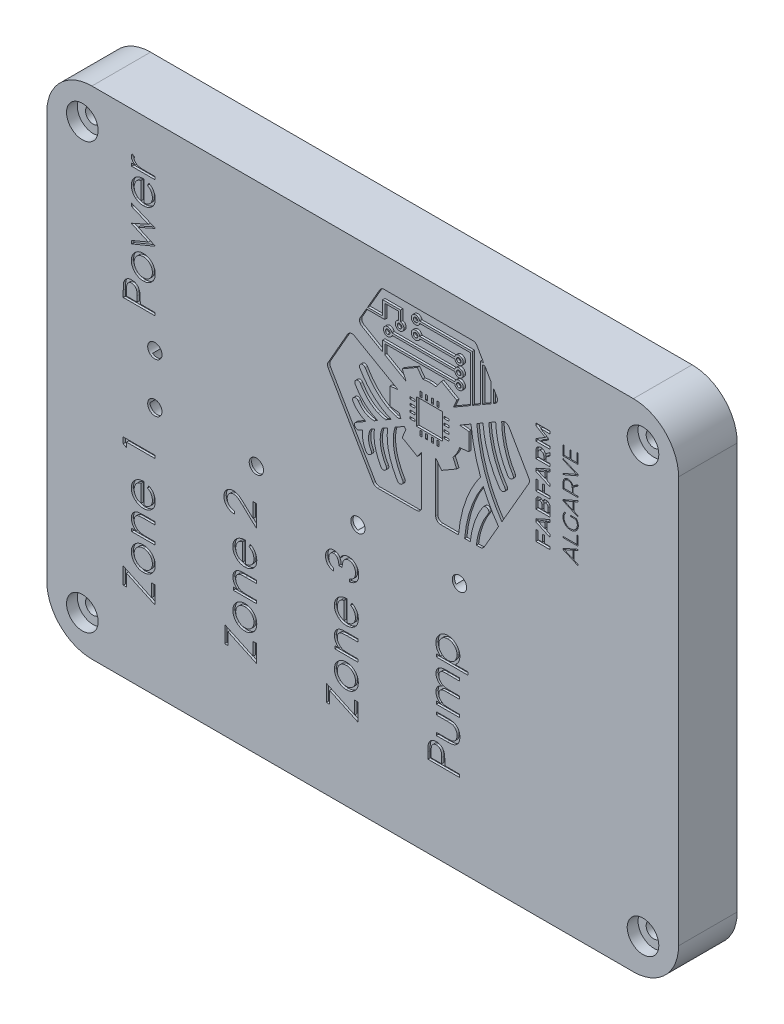
SolidWorks part; units mm, degrees
ref_plane "Front Plane" through (0, 0, 0) normal (0, 0, 1) x (1, 0, 0)
ref_plane "Top Plane" through (0, 0, 0) normal (0, 1, 0) x (1, 0, 0)
ref_plane "Right Plane" through (0, 0, 0) normal (1, 0, 0) x (0, 0, -1)
sketch "Sketch1" plane through (0, 0, 0) normal (0, 0, 1) x (1, 0, 0)
  line L0 (128.6764, 77.0848) -> (128.6764, -12.9152) construction
  line L1 (118.6764, -22.9152) -> (-1.3236, -22.9152) construction
  line L2 (-11.3236, -12.9152) -> (-11.3236, 77.0848) construction
  line L3 (-1.3236, 87.0848) -> (118.6764, 87.0848) construction
  line L4 (128.6764, 77.0848) -> (128.6764, -12.9152)
  line L5 (118.6764, -22.9152) -> (-1.3236, -22.9152)
  line L6 (-11.3236, -12.9152) -> (-11.3236, 77.0848)
  line L7 (-1.3236, 87.0848) -> (118.6764, 87.0848)
  arc A0 (128.6764, 77.0848) -> (118.6764, 87.0848) centre (118.6764, 77.0848) ccw construction
  arc A1 (118.6764, -22.9152) -> (128.6764, -12.9152) centre (118.6764, -12.9152) ccw construction
  arc A2 (-11.3236, -12.9152) -> (-1.3236, -22.9152) centre (-1.3236, -12.9152) ccw construction
  arc A3 (-1.3236, 87.0848) -> (-11.3236, 77.0848) centre (-1.3236, 77.0848) ccw construction
  arc A4 (128.6764, 77.0848) -> (118.6764, 87.0848) centre (118.6764, 77.0848) ccw
  arc A5 (118.6764, -22.9152) -> (128.6764, -12.9152) centre (118.6764, -12.9152) ccw
  arc A6 (-11.3236, -12.9152) -> (-1.3236, -22.9152) centre (-1.3236, -12.9152) ccw
  arc A7 (-1.3236, 87.0848) -> (-11.3236, 77.0848) centre (-1.3236, 77.0848) ccw
extrude "Boss-Extrude1" add sketch "Sketch1" along normal offset from surface (13 mm away) 6 offset beyond the face yes
sketch "Sketch12" plane through (0, 0, 0) normal (0, 0, -1) x (-1, 0, 0)
  line L8 (1.3236, -6.9152) -> (1.3236, 70.5848)
  line L9 (-5.1764, 77.0848) -> (-109.6764, 77.0848)
  line L10 (-118.6764, 68.0848) -> (-118.6764, -3.9152)
  line L11 (-109.6764, -12.9152) -> (-7.6764, -12.9152)
  line L16 (-5.1764, 74.0848) -> (-5.1764, 77.0848)
  line L18 (-1.6764, -6.9152) -> (1.3236, -6.9152)
  line L20 (1.3236, 70.5848) -> (-1.6764, 70.5848)
  arc A25 (-5.1764, 74.0848) -> (-1.6764, 70.5848) centre (-1.6764, 74.0848) ccw
  arc A27 (-109.6764, 77.0848) -> (-112.6764, 74.0848) centre (-109.6764, 74.0848) ccw
  arc A28 (-115.6764, 71.0848) -> (-112.6764, 74.0848) centre (-115.6764, 74.0848) ccw
  arc A29 (-115.6764, 71.0848) -> (-118.6764, 68.0848) centre (-115.6764, 68.0848) ccw
  arc A30 (-118.6764, -3.9152) -> (-115.6764, -6.9152) centre (-115.6764, -3.9152) ccw
  arc A31 (-112.6764, -9.9152) -> (-115.6764, -6.9152) centre (-115.6764, -9.9152) ccw
  arc A32 (-112.6764, -9.9152) -> (-109.6764, -12.9152) centre (-109.6764, -9.9152) ccw
  arc A33 (-7.6764, -12.9152) -> (-4.6764, -9.9152) centre (-7.6764, -9.9152) ccw
  arc A34 (-1.6764, -6.9152) -> (-4.6764, -9.9152) centre (-1.6764, -9.9152) ccw
extrude "Cut-Extrude6" [suppressed] cut sketch "Sketch12" against normal offset from surface (10 mm away) 3 up to face at (58.6764, 32.0848, 13)
sketch "Sketch2" plane through (0, 0, 0) normal (0, 0, -1) x (-1, 0, 0)
  line L2 (1.3236, -6.9152) -> (1.3236, 70.5848)
  line L34 (-5.1764, 77.0848) -> (-109.6764, 77.0848)
  line L35 (-118.6764, 68.0848) -> (-118.6764, -3.9152)
  line L36 (-109.6764, -12.9152) -> (-7.6764, -12.9152)
  line L37 (-5.1764, 74.0848) -> (-5.1764, 77.0848)
  line L38 (-1.6764, -6.9152) -> (1.3236, -6.9152)
  line L39 (1.3236, 70.5848) -> (-1.6764, 70.5848)
  arc A0 (-5.1764, 74.0848) -> (-1.6764, 70.5848) centre (-1.6764, 74.0848) ccw
  arc A1 (-109.6764, 77.0848) -> (-112.6764, 74.0848) centre (-109.6764, 74.0848) ccw
  arc A2 (-115.6764, 71.0848) -> (-112.6764, 74.0848) centre (-115.6764, 74.0848) ccw
  arc A3 (-115.6764, 71.0848) -> (-118.6764, 68.0848) centre (-115.6764, 68.0848) ccw
  arc A4 (-118.6764, -3.9152) -> (-115.6764, -6.9152) centre (-115.6764, -3.9152) ccw
  arc A5 (-112.6764, -9.9152) -> (-115.6764, -6.9152) centre (-115.6764, -9.9152) ccw
  arc A14 (-112.6764, -9.9152) -> (-109.6764, -12.9152) centre (-109.6764, -9.9152) ccw
  arc A23 (-7.6764, -12.9152) -> (-4.6764, -9.9152) centre (-7.6764, -9.9152) ccw
  arc A24 (-1.6764, -6.9152) -> (-4.6764, -9.9152) centre (-1.6764, -9.9152) ccw
  point P57 (-115.6764, -9.9152)
extrude "Cut-Extrude1" cut sketch "Sketch2" against normal offset from surface (10 mm away) 3 up to face at (58.6764, 32.0848, 13)
hole_wizard "CBORE for M3 Pan Head Screw1" positions "Sketch3" profile "Sketch4" counterbore size "M3" standard "ISO"
sketch "Sketch3" plane through (0, 0, 13) normal (0, 0, 1) x (1, 0, 0)
  point P0 (-3.4449, -15.0365)
  point P3 (120.7977, -15.0365)
  point P6 (120.7977, 79.2061)
  point P9 (-3.4449, 79.2061)
sketch "Sketch4" plane through (-3.4449, -15.0365, 13) normal (1, 0, 0) x (0, -1, 0)
  line L0 (0, 0) -> (0, 16.0215)
  line L1 (0, 16.0215) -> (1.7, 15)
  line L2 (1.7, 15) -> (1.7, 2.4)
  line L3 (1.7, 2.4) -> (3.5, 2.4)
  line L4 (3.5, 2.4) -> (3.5, 0)
  line L5 (3.5, 0) -> (0, 0)
  line L10 (0, 16.0215) -> (-1.7, 15) construction
  line L11 (0, -6.35) -> (0, 107.95) construction
  dimension "Hole Dia." = 3.4
  dimension "Hole Depth" = 15
  dimension "C'Bore Dia." = 7
  dimension "C'Bore Depth" = 2.4
  dimension "Drill Angle" = 118
fillet "Fillet1" radius 3 3 edges at (-1.3236, -6.9152, 5) (-1.3236, 70.5848, 5) (5.1764, 77.0848, 5)
sketch "Sketch5" plane through (0, 0, 13) normal (0, 0, 1) x (1, 0, 0)
  line L0 (12.6214, 32.3367) -> (99.9994, 32.3367) construction
  line L1 (99.9994, 0) -> (99.9994, 70) construction
  line L2 (12.6214, 32.3367) -> (12.6214, 48.4676) construction
  line L9 (12.6214, 33.064) -> (12.6214, 29) construction
  line L10 (11.6054, 33.064) -> (13.6374, 33.064) construction
  line L11 (13.6374, 29) -> (11.6054, 29) construction
  line L12 (60.1722, 44.4436) -> (58.5466, 44.4436) construction
  line L13 (60.1722, 45.4025) -> (60.1722, 43.4848) construction
  line L14 (58.5466, 45.4025) -> (58.5466, 43.4848) construction
  line L15 (59.3594, 44.4436) -> (59.3594, 47.8324) construction
  circle A0 centre (12.6214, 32.3367) radius 1.5875
  circle A1 centre (35.1214, 32.3367) radius 1.5875
  circle A2 centre (57.6214, 32.3367) radius 1.5875
  circle A3 centre (80.1214, 32.3367) radius 1.5875
  circle A4 centre (12.6214, 43.2728) radius 1.5875
  dimension "D1" = 3.175
  dimension "D2" = 3.175
  dimension "D3" = 3.175
  dimension "D4" = 3.175
  dimension "D8" = 3.175
  dimension "D5" = 22.5
  dimension "D6" = 22.5
  dimension "D7" = 22.5
extrude "Cut-Extrude2" cut sketch "Sketch5" against normal blind 2.5
sketch "Sketch6" plane through (0, 0, 10) normal (0, 0, -1) x (-1, 0, 0)
  circle A0 centre (-12.6214, 31.032) radius 2
  circle A1 centre (-35.2293, 31.7818) radius 2
  circle A2 centre (-55.3902, 31.7818) radius 2
  circle A3 centre (-79.0825, 33.3273) radius 2
  circle A4 centre (-12.0944, 40.0848) radius 2
  dimension "D1" = 4
  dimension "D2" = 4
  dimension "D3" = 4
extrude "Cut-Extrude3" cut sketch "Sketch6" against normal blind 2.5
sketch "Sketch8" plane through (0, 0, 10) normal (0, 0, -1) x (-1, 0, 0)
  line L6 (1.3236, -3.9152) -> (1.3236, 67.5848)
  line L7 (1.3236, -3.9152) -> (1.3236, 67.5848)
  line L19 (-8.1764, 77.0848) -> (-109.6764, 77.0848)
  line L20 (-8.1764, 77.0848) -> (-109.6764, 77.0848)
  line L21 (-118.6764, 68.0848) -> (-118.6764, -3.9152)
  line L22 (-118.6764, 68.0848) -> (-118.6764, -3.9152)
  line L23 (-109.6764, -12.9152) -> (-7.6764, -12.9152)
  line L24 (-109.6764, -12.9152) -> (-7.6764, -12.9152)
  circle A0 centre (-12.0944, 40.0848) radius 4
  circle A1 centre (-12.0944, 40.0848) radius 2 construction
  circle A2 centre (-12.0944, 40.0848) radius 2
  arc A9 (-5.1764, 74.0848) -> (-1.6764, 70.5848) centre (-1.6764, 74.0848) ccw
  arc A10 (-5.1764, 74.0848) -> (-1.6764, 70.5848) centre (-1.6764, 74.0848) ccw
  arc A11 (-109.6764, 77.0848) -> (-112.6764, 74.0848) centre (-109.6764, 74.0848) ccw
  arc A12 (-109.6764, 77.0848) -> (-112.6764, 74.0848) centre (-109.6764, 74.0848) ccw
  arc A13 (-115.6764, 71.0848) -> (-112.6764, 74.0848) centre (-115.6764, 74.0848) ccw
  arc A14 (-115.6764, 71.0848) -> (-112.6764, 74.0848) centre (-115.6764, 74.0848) ccw
  arc A15 (-115.6764, 71.0848) -> (-118.6764, 68.0848) centre (-115.6764, 68.0848) ccw
  arc A16 (-115.6764, 71.0848) -> (-118.6764, 68.0848) centre (-115.6764, 68.0848) ccw
  arc A17 (-118.6764, -3.9152) -> (-115.6764, -6.9152) centre (-115.6764, -3.9152) ccw
  arc A18 (-118.6764, -3.9152) -> (-115.6764, -6.9152) centre (-115.6764, -3.9152) ccw
  arc A19 (-112.6764, -9.9152) -> (-115.6764, -6.9152) centre (-115.6764, -9.9152) ccw
  arc A20 (-112.6764, -9.9152) -> (-115.6764, -6.9152) centre (-115.6764, -9.9152) ccw
  arc A21 (-112.6764, -9.9152) -> (-109.6764, -12.9152) centre (-109.6764, -9.9152) ccw
  arc A22 (-112.6764, -9.9152) -> (-109.6764, -12.9152) centre (-109.6764, -9.9152) ccw
  arc A23 (-7.6764, -12.9152) -> (-4.6764, -9.9152) centre (-7.6764, -9.9152) ccw
  arc A36 (-7.6764, -12.9152) -> (-4.6764, -9.9152) centre (-7.6764, -9.9152) ccw
  arc A37 (-1.6764, -6.9152) -> (-4.6764, -9.9152) centre (-1.6764, -9.9152) ccw
  arc A38 (-1.6764, -6.9152) -> (-4.6764, -9.9152) centre (-1.6764, -9.9152) ccw
  arc A42 (-1.6764, -6.9152) -> (1.3236, -3.9152) centre (-1.6764, -3.9152) ccw
  arc A43 (-1.6764, -6.9152) -> (1.3236, -3.9152) centre (-1.6764, -3.9152) ccw
  arc A44 (1.3236, 67.5848) -> (-1.6764, 70.5848) centre (-1.6764, 67.5848) ccw
  arc A45 (1.3236, 67.5848) -> (-1.6764, 70.5848) centre (-1.6764, 67.5848) ccw
  arc A46 (-5.1764, 74.0848) -> (-8.1764, 77.0848) centre (-8.1764, 74.0848) ccw
  arc A47 (-5.1764, 74.0848) -> (-8.1764, 77.0848) centre (-8.1764, 74.0848) ccw
  circle A95 centre (-12.6214, 31.032) radius 2 construction
  circle A98 centre (-12.6214, 31.032) radius 2
  circle A101 centre (-35.2293, 31.7818) radius 2 construction
  circle A106 centre (-35.2293, 31.7818) radius 2
  circle A115 centre (-55.3902, 31.7818) radius 2 construction
  circle A116 centre (-55.3902, 31.7818) radius 2
  circle A117 centre (-79.0825, 33.3273) radius 2 construction
  circle A118 centre (-79.0825, 33.3273) radius 2
  circle A119 centre (-12.6214, 31.032) radius 4
  circle A120 centre (-35.2293, 31.7818) radius 4
  circle A121 centre (-55.3902, 31.7818) radius 4
  circle A122 centre (-79.0825, 33.3273) radius 4
  circle M21 centre (-12.6214, 31.032) radius 2
  circle M22 centre (-55.3902, 31.7818) radius 2
  circle M23 centre (-35.2293, 31.7818) radius 2
  circle M24 centre (-79.0825, 33.3273) radius 2
  dimension "D3" = 2
  dimension "D1" = 0
  dimension "D2" = 2
extrude "Boss-Extrude2" add sketch "Sketch8" along normal offset from surface (6.3048 mm away) 1 contours A122 M24 | A121 M22 | A120 M23 | A119 M21 region at (16.5083, 31.032, 10) region at (39.1162, 31.7818, 10) region at (59.277, 31.7818, 10) region at (82.9694, 33.3273, 10)
sketch "Sketch10" plane through (0, 0, 0) normal (0, 0, -1) x (-1, 0, 0)
  line L0 (-121.1764, 74.0848) -> (-120.1764, 74.0848)
  line L1 (-115.6764, 78.5848) -> (-115.6764, 79.5848)
  line L2 (-111.1764, 84.0848) -> (-6.1764, 84.0848)
  line L3 (-1.6764, 79.5848) -> (-1.6764, 78.5848)
  line L21 (2.8236, 74.0848) -> (3.8236, 74.0848)
  line L22 (8.3236, 69.5848) -> (8.3236, -5.4152)
  line L23 (3.8236, -9.9152) -> (2.8236, -9.9152)
  line L24 (-1.6764, -14.4152) -> (-1.6764, -15.4152)
  line L25 (-6.1764, -19.9152) -> (-111.1764, -19.9152)
  line L26 (-115.6764, -15.4152) -> (-115.6764, -14.4152)
  line L27 (-120.1764, -9.9152) -> (-121.1764, -9.9152)
  line L28 (-125.6764, -5.4152) -> (-125.6764, 69.5848)
  line L918 (-121.1764, 73.0848) -> (-120.1764, 73.0848)
  line L919 (-121.1764, 73.0848) -> (-120.1764, 73.0848)
  line L926 (-114.6764, 78.5848) -> (-114.6764, 79.5848)
  line L927 (-111.1764, 83.0848) -> (-6.1764, 83.0848)
  line L928 (-2.6764, 79.5848) -> (-2.6764, 78.5848)
  line L929 (2.8236, 73.0848) -> (3.8236, 73.0848)
  line L930 (7.3236, 69.5848) -> (7.3236, -5.4152)
  line L931 (3.8236, -8.9152) -> (2.8236, -8.9152)
  line L932 (-2.6764, -14.4152) -> (-2.6764, -15.4152)
  line L933 (-6.1764, -18.9152) -> (-111.1764, -18.9152)
  line L934 (-114.6764, -15.4152) -> (-114.6764, -14.4152)
  line L935 (-120.1764, -8.9152) -> (-121.1764, -8.9152)
  line L936 (-124.6764, -5.4152) -> (-124.6764, 69.5848)
  line L937 (-114.6764, 78.5848) -> (-114.6764, 79.5848)
  line L938 (-111.1764, 83.0848) -> (-6.1764, 83.0848)
  line L939 (-2.6764, 79.5848) -> (-2.6764, 78.5848)
  line L940 (2.8236, 73.0848) -> (3.8236, 73.0848)
  line L941 (7.3236, 69.5848) -> (7.3236, -5.4152)
  line L942 (3.8236, -8.9152) -> (2.8236, -8.9152)
  line L943 (-2.6764, -14.4152) -> (-2.6764, -15.4152)
  line L944 (-6.1764, -18.9152) -> (-111.1764, -18.9152)
  line L945 (-114.6764, -15.4152) -> (-114.6764, -14.4152)
  line L946 (-120.1764, -8.9152) -> (-121.1764, -8.9152)
  line L947 (-124.6764, -5.4152) -> (-124.6764, 69.5848)
  arc A0 (-120.1764, 74.0848) -> (-115.6764, 78.5848) centre (-120.1764, 78.5848) ccw
  arc A1 (-111.1764, 84.0848) -> (-115.6764, 79.5848) centre (-111.1764, 79.5848) ccw
  arc A2 (-1.6764, 79.5848) -> (-6.1764, 84.0848) centre (-6.1764, 79.5848) ccw
  arc A3 (-1.6764, 78.5848) -> (2.8236, 74.0848) centre (2.8236, 78.5848) ccw
  arc A16 (8.3236, 69.5848) -> (3.8236, 74.0848) centre (3.8236, 69.5848) ccw
  arc A17 (3.8236, -9.9152) -> (8.3236, -5.4152) centre (3.8236, -5.4152) ccw
  arc A18 (2.8236, -9.9152) -> (-1.6764, -14.4152) centre (2.8236, -14.4152) ccw
  arc A19 (-6.1764, -19.9152) -> (-1.6764, -15.4152) centre (-6.1764, -15.4152) ccw
  arc A20 (-115.6764, -15.4152) -> (-111.1764, -19.9152) centre (-111.1764, -15.4152) ccw
  arc A21 (-115.6764, -14.4152) -> (-120.1764, -9.9152) centre (-120.1764, -14.4152) ccw
  arc A22 (-125.6764, -5.4152) -> (-121.1764, -9.9152) centre (-121.1764, -5.4152) ccw
  arc A23 (-121.1764, 74.0848) -> (-125.6764, 69.5848) centre (-121.1764, 69.5848) ccw
  arc A1014 (-121.1764, 73.0848) -> (-124.6764, 69.5848) centre (-121.1764, 69.5848) ccw
  arc A1015 (-121.1764, 73.0848) -> (-124.6764, 69.5848) centre (-121.1764, 69.5848) ccw
  arc A1023 (-120.1764, 73.0848) -> (-114.6764, 78.5848) centre (-120.1764, 78.5848) ccw
  arc A1024 (-111.1764, 83.0848) -> (-114.6764, 79.5848) centre (-111.1764, 79.5848) ccw
  arc A1025 (-2.6764, 79.5848) -> (-6.1764, 83.0848) centre (-6.1764, 79.5848) ccw
  arc A1026 (-2.6764, 78.5848) -> (2.8236, 73.0848) centre (2.8236, 78.5848) ccw
  arc A1027 (7.3236, 69.5848) -> (3.8236, 73.0848) centre (3.8236, 69.5848) ccw
  arc A1028 (3.8236, -8.9152) -> (7.3236, -5.4152) centre (3.8236, -5.4152) ccw
  arc A1029 (2.8236, -8.9152) -> (-2.6764, -14.4152) centre (2.8236, -14.4152) ccw
  arc A1030 (-6.1764, -18.9152) -> (-2.6764, -15.4152) centre (-6.1764, -15.4152) ccw
  arc A1031 (-114.6764, -15.4152) -> (-111.1764, -18.9152) centre (-111.1764, -15.4152) ccw
  arc A1032 (-114.6764, -14.4152) -> (-120.1764, -8.9152) centre (-120.1764, -14.4152) ccw
  arc A1033 (-124.6764, -5.4152) -> (-121.1764, -8.9152) centre (-121.1764, -5.4152) ccw
  arc A1034 (-120.1764, 73.0848) -> (-114.6764, 78.5848) centre (-120.1764, 78.5848) ccw
  arc A1035 (-111.1764, 83.0848) -> (-114.6764, 79.5848) centre (-111.1764, 79.5848) ccw
  arc A1036 (-2.6764, 79.5848) -> (-6.1764, 83.0848) centre (-6.1764, 79.5848) ccw
  arc A1037 (-2.6764, 78.5848) -> (2.8236, 73.0848) centre (2.8236, 78.5848) ccw
  arc A1038 (7.3236, 69.5848) -> (3.8236, 73.0848) centre (3.8236, 69.5848) ccw
  arc A1039 (3.8236, -8.9152) -> (7.3236, -5.4152) centre (3.8236, -5.4152) ccw
  arc A1040 (2.8236, -8.9152) -> (-2.6764, -14.4152) centre (2.8236, -14.4152) ccw
  arc A1041 (-6.1764, -18.9152) -> (-2.6764, -15.4152) centre (-6.1764, -15.4152) ccw
  arc A1042 (-114.6764, -15.4152) -> (-111.1764, -18.9152) centre (-111.1764, -15.4152) ccw
  arc A1043 (-114.6764, -14.4152) -> (-120.1764, -8.9152) centre (-120.1764, -14.4152) ccw
  arc A1044 (-124.6764, -5.4152) -> (-121.1764, -8.9152) centre (-121.1764, -5.4152) ccw
  dimension "D1" = 1
  dimension "D2" = 1
  dimension "D3" = 1
extrude "Boss-Extrude3" add sketch "Sketch10" along normal blind 0.5 contours L21 L24 A18 A17 L22 A16 L0 A0 region at (120.6764, 73.9152, 0)
sketch "Sketch7" plane through (0, 0, 13) normal (0, 0, 1) x (1, 0, 0)
  line L0 (97.5311, 49.4647) -> (98.5063, 49.4647)
  line L1 (98.5063, 49.4647) -> (98.5063, 51.0118)
  line L2 (98.5063, 51.0118) -> (99.01, 51.0118)
  line L3 (99.01, 51.0118) -> (99.01, 49.4647)
  line L4 (99.01, 49.4647) -> (100.2376, 49.4647)
  line L5 (100.2376, 49.4647) -> (100.2376, 48.8694)
  line L6 (100.2376, 48.8694) -> (97.0323, 48.8694)
  line L7 (97.0323, 48.8694) -> (97.0323, 51.2096)
  line L8 (97.0323, 51.2096) -> (97.5311, 51.2096)
  line L9 (97.5311, 51.2096) -> (97.5311, 49.4647)
  line L10 (99.4952, 53.7281) -> (99.4952, 52.1254)
  line L11 (99.4952, 52.1254) -> (100.2366, 51.8097)
  line L12 (100.2366, 51.8097) -> (100.2366, 51.196)
  line L13 (100.2366, 51.196) -> (97.0313, 52.6379)
  line L14 (97.0313, 52.6379) -> (97.0313, 53.2244)
  line L15 (97.0313, 53.2244) -> (100.2366, 54.6712)
  line L16 (100.2366, 54.6712) -> (100.2366, 54.0486)
  line L17 (100.2366, 54.0486) -> (99.4952, 53.7281)
  line L18 (99.0285, 53.5313) -> (97.6275, 52.9272)
  line L19 (97.6275, 52.9272) -> (99.0285, 52.3271)
  line L20 (99.0285, 52.3271) -> (99.0285, 53.5313)
  line L21 (100.2376, 56.6723) -> (100.2376, 55.0794)
  line L22 (100.2376, 55.0794) -> (97.0323, 55.0794)
  line L23 (97.0323, 55.0794) -> (97.0323, 56.5817)
  line L24 (97.4989, 55.6737) -> (98.3826, 55.6737)
  line L25 (98.3826, 55.6737) -> (98.3826, 56.5164)
  line L26 (97.4989, 56.5164) -> (97.4989, 55.6737)
  line L27 (98.8454, 56.6353) -> (98.8454, 55.6737)
  line L28 (98.8454, 55.6737) -> (99.7699, 55.6737)
  line L29 (99.7699, 55.6737) -> (99.7699, 56.6353)
  line L30 (97.5311, 59.1586) -> (98.5063, 59.1586)
  line L31 (98.5063, 59.1586) -> (98.5063, 60.7067)
  line L32 (98.5063, 60.7067) -> (99.01, 60.7067)
  line L33 (99.01, 60.7067) -> (99.01, 59.1586)
  line L34 (99.01, 59.1586) -> (100.2376, 59.1586)
  line L35 (100.2376, 59.1586) -> (100.2376, 58.5633)
  line L36 (100.2376, 58.5633) -> (97.0323, 58.5633)
  line L37 (97.0323, 58.5633) -> (97.0323, 60.9035)
  line L38 (97.0323, 60.9035) -> (97.5311, 60.9035)
  line L39 (97.5311, 60.9035) -> (97.5311, 59.1586)
  line L40 (99.4952, 63.422) -> (99.4952, 61.8193)
  line L41 (99.4952, 61.8193) -> (100.2366, 61.5037)
  line L42 (100.2366, 61.5037) -> (100.2366, 60.8899)
  line L43 (100.2366, 60.8899) -> (97.0313, 62.3318)
  line L44 (97.0313, 62.3318) -> (97.0313, 62.9183)
  line L45 (97.0313, 62.9183) -> (100.2366, 64.3651)
  line L46 (100.2366, 64.3651) -> (100.2366, 63.7425)
  line L47 (100.2366, 63.7425) -> (99.4952, 63.422)
  line L48 (99.0285, 63.2242) -> (97.6275, 62.6202)
  line L49 (97.6275, 62.6202) -> (99.0285, 62.02)
  line L50 (99.0285, 62.02) -> (99.0285, 63.2242)
  line L51 (100.2376, 66.8699) -> (99.2994, 66.2152)
  line L52 (99.3042, 66.0915) -> (99.3042, 65.3676)
  line L53 (99.3042, 65.3676) -> (100.2386, 65.3676)
  line L54 (100.2386, 65.3676) -> (100.2386, 64.7723)
  line L55 (100.2386, 64.7723) -> (97.0332, 64.7723)
  line L56 (97.0332, 64.7723) -> (97.0332, 66.0915)
  line L57 (99.1854, 66.7744) -> (100.2386, 67.5119)
  line L58 (100.2386, 67.5119) -> (100.2386, 66.8699)
  line L59 (100.2386, 66.8699) -> (100.2376, 66.8699)
  line L60 (97.536, 66.0632) -> (97.536, 65.3676)
  line L61 (97.536, 65.3676) -> (98.8132, 65.3676)
  line L62 (98.8132, 65.3676) -> (98.8132, 66.0632)
  line L63 (100.2376, 71.0641) -> (98.1127, 71.0592)
  line L64 (98.1127, 71.0592) -> (99.8713, 70.006)
  line L65 (99.8713, 70.006) -> (99.8713, 69.7401)
  line L66 (99.8713, 69.7401) -> (98.141, 68.6869)
  line L67 (98.141, 68.6869) -> (100.2376, 68.6869)
  line L68 (100.2376, 68.6869) -> (100.2376, 68.1189)
  line L69 (100.2376, 68.1189) -> (97.0323, 68.1189)
  line L70 (97.0323, 68.1189) -> (97.0323, 68.609)
  line L71 (97.0323, 68.609) -> (99.1571, 69.8823)
  line L72 (99.1571, 69.8823) -> (97.0323, 71.1323)
  line L73 (97.0323, 71.1323) -> (97.0323, 71.6223)
  line L74 (97.0323, 71.6223) -> (100.2376, 71.6272)
  line L75 (100.2376, 71.6272) -> (100.2376, 71.0641)
  line L76 (105.4922, 51.3869) -> (105.4922, 49.528)
  line L77 (105.4922, 49.528) -> (106.4392, 49.1208)
  line L78 (106.4392, 49.1208) -> (106.4392, 48.8694)
  line L79 (106.4392, 48.8694) -> (103.0741, 50.3435)
  line L80 (103.0741, 50.3435) -> (103.0741, 50.5773)
  line L81 (103.0741, 50.5773) -> (106.4392, 52.0514)
  line L82 (106.4392, 52.0514) -> (106.4392, 51.8)
  line L83 (106.4392, 51.8) -> (105.4922, 51.3869)
  line L84 (105.2857, 51.3002) -> (103.343, 50.4575)
  line L85 (103.343, 50.4575) -> (105.2857, 49.6196)
  line L86 (105.2857, 49.6196) -> (105.2857, 51.3002)
  line L87 (103.0741, 52.6194) -> (103.0741, 52.8532)
  line L88 (103.0741, 52.8532) -> (106.2181, 52.8532)
  line L89 (106.2181, 52.8532) -> (106.2181, 54.6984)
  line L90 (106.2181, 54.6984) -> (106.4392, 54.6984)
  line L91 (106.4392, 54.6984) -> (106.4392, 52.6194)
  line L92 (106.4392, 52.6194) -> (103.0741, 52.6194)
  line L93 (104.7713, 57.5092) -> (104.7713, 57.7333)
  line L94 (104.7713, 57.7333) -> (106.031, 57.7333)
  line L95 (103.5116, 57.7469) -> (103.6752, 57.6008)
  line L96 (105.9297, 57.5092) -> (104.7713, 57.5092)
  line L97 (105.4922, 60.7281) -> (105.4922, 58.8692)
  line L98 (105.4922, 58.8692) -> (106.4392, 58.462)
  line L99 (106.4392, 58.462) -> (106.4392, 58.2106)
  line L100 (106.4392, 58.2106) -> (103.0741, 59.6847)
  line L101 (103.0741, 59.6847) -> (103.0741, 59.9185)
  line L102 (103.0741, 59.9185) -> (106.4392, 61.3926)
  line L103 (106.4392, 61.3926) -> (106.4392, 61.1412)
  line L104 (106.4392, 61.1412) -> (105.4922, 60.7281)
  line L105 (105.2857, 60.6414) -> (103.343, 59.7987)
  line L106 (103.343, 59.7987) -> (105.2857, 58.9608)
  line L107 (105.2857, 58.9608) -> (105.2857, 60.6414)
  line L108 (106.4392, 64.1858) -> (105.3139, 63.421)
  line L109 (105.3383, 63.1092) -> (105.3383, 62.1934)
  line L110 (105.3383, 62.1934) -> (106.4392, 62.1934)
  line L111 (106.4392, 62.1934) -> (106.4392, 61.9596)
  line L112 (106.4392, 61.9596) -> (103.0741, 61.9596)
  line L113 (103.0741, 61.9596) -> (103.0741, 63.1092)
  line L114 (105.2623, 63.649) -> (106.4402, 64.4498)
  line L115 (106.4402, 64.4498) -> (106.4402, 64.1858)
  line L116 (106.4402, 64.1858) -> (106.4392, 64.1858)
  line L117 (103.2943, 63.1092) -> (103.2943, 62.1934)
  line L118 (103.2943, 62.1934) -> (105.121, 62.1934)
  line L119 (105.121, 62.1934) -> (105.121, 63.1092)
  line L120 (105.121, 63.1092) -> (105.122, 63.1092)
  line L121 (103.0741, 67.8032) -> (106.4392, 66.375)
  line L122 (106.4392, 66.375) -> (106.4392, 66.1411)
  line L123 (106.4392, 66.1411) -> (103.0741, 64.7129)
  line L124 (103.0741, 64.7129) -> (103.0741, 64.9691)
  line L125 (103.0741, 64.9691) -> (106.1226, 66.2649)
  line L126 (106.1226, 66.2649) -> (103.0741, 67.5606)
  line L127 (103.0741, 67.5606) -> (103.0741, 67.8032)
  line L128 (106.2181, 70.5185) -> (106.4392, 70.5185)
  line L129 (106.4392, 70.5185) -> (106.4392, 68.3069)
  line L130 (106.4392, 68.3069) -> (103.0741, 68.3069)
  line L131 (103.0741, 68.3069) -> (103.0741, 70.4503)
  line L132 (103.0741, 70.4503) -> (103.2953, 70.4503)
  line L133 (103.2953, 70.4503) -> (103.2953, 68.5408)
  line L134 (103.2953, 68.5408) -> (104.6222, 68.5408)
  line L135 (104.6222, 68.5408) -> (104.6222, 70.2486)
  line L136 (104.6222, 70.2486) -> (104.8385, 70.2486)
  line L137 (104.8385, 70.2486) -> (104.8385, 68.5408)
  line L138 (104.8385, 68.5408) -> (106.2181, 68.5408)
  line L139 (106.2181, 68.5408) -> (106.2181, 70.5185)
  line L140 (71.7348, 42.7356) -> (71.6787, 53.2796)
  line L141 (71.6787, 53.2796) -> (70.7914, 52.0642)
  line L142 (70.7914, 52.0642) -> (67.4269, 54.0038)
  line L143 (67.4269, 54.0038) -> (68.2526, 55.8825)
  line L144 (66.7815, 58.4286) -> (64.7436, 58.6559)
  line L145 (64.7436, 58.6559) -> (64.7436, 62.5351)
  line L146 (64.7436, 62.5351) -> (66.4892, 62.7299)
  line L147 (66.4892, 62.7299) -> (56.8732, 68.2183)
  line L148 (55.3501, 67.8018) -> (51.0398, 60.2504)
  line L149 (51.0455, 59.1341) -> (60.9805, 42.1235)
  line L150 (61.9499, 41.5698) -> (70.6233, 41.6128)
  line L151 (82.6765, 64.21) -> (80.1703, 62.7624)
  line L152 (80.1703, 62.7624) -> (82.2008, 62.5359)
  line L153 (82.2008, 62.5359) -> (82.2008, 58.6567)
  line L154 (82.2008, 58.6567) -> (80.1629, 58.4294)
  line L155 (78.6934, 55.8833) -> (79.5191, 54.0046)
  line L156 (79.5191, 54.0046) -> (76.1547, 52.065)
  line L157 (76.1547, 52.065) -> (74.9425, 53.7245)
  line L158 (74.8459, 53.7066) -> (74.8459, 42.6804)
  line L159 (75.9623, 41.5641) -> (79.9169, 41.5641)
  line L160 (88.147, 67.3699) -> (86.6174, 66.4857)
  line L161 (85.3225, 65.7371) -> (83.9585, 64.9488)
  line L162 (89.5224, 48.8694) -> (95.4751, 59.1796)
  line L163 (95.4751, 60.2959) -> (91.1388, 67.8075)
  line L164 (89.6133, 68.2158) -> (89.4761, 68.1387)
  line L165 (81.272, 41.5633) -> (82.5182, 41.5633)
  line L166 (83.8773, 41.5624) -> (84.6575, 41.5624)
  line L167 (85.6245, 42.121) -> (88.7762, 47.5801)
  line L168 (69.1781, 58.4659) -> (69.1781, 58.9003)
  line L169 (69.1781, 58.9003) -> (70.2628, 58.9003)
  line L170 (70.2628, 58.9003) -> (70.2628, 58.4659)
  line L171 (70.2628, 58.4659) -> (69.1781, 58.4659)
  line L172 (69.1781, 59.7414) -> (69.1781, 60.1757)
  line L173 (69.1781, 60.1757) -> (70.2628, 60.1757)
  line L174 (70.2628, 60.1757) -> (70.2628, 59.7414)
  line L175 (70.2628, 59.7414) -> (69.1781, 59.7414)
  line L176 (69.1781, 61.0168) -> (69.1781, 61.4512)
  line L177 (69.1781, 61.4512) -> (70.2628, 61.4512)
  line L178 (70.2628, 61.4512) -> (70.2628, 61.0168)
  line L179 (70.2628, 61.0168) -> (69.1781, 61.0168)
  line L180 (69.1781, 62.2923) -> (69.1781, 62.7267)
  line L181 (69.1781, 62.7267) -> (70.2628, 62.7267)
  line L182 (70.2628, 62.7267) -> (70.2628, 62.2923)
  line L183 (70.2628, 62.2923) -> (69.1781, 62.2923)
  line L184 (76.6824, 58.4659) -> (76.6824, 58.9003)
  line L185 (76.6824, 58.9003) -> (77.7671, 58.9003)
  line L186 (77.7671, 58.9003) -> (77.7671, 58.4659)
  line L187 (77.7671, 58.4659) -> (76.6824, 58.4659)
  line L188 (76.6824, 59.7414) -> (76.6824, 60.1757)
  line L189 (76.6824, 60.1757) -> (77.7671, 60.1757)
  line L190 (77.7671, 60.1757) -> (77.7671, 59.7414)
  line L191 (77.7671, 59.7414) -> (76.6824, 59.7414)
  line L192 (76.6824, 61.0168) -> (76.6824, 61.4512)
  line L193 (76.6824, 61.4512) -> (77.7671, 61.4512)
  line L194 (77.7671, 61.4512) -> (77.7671, 61.0168)
  line L195 (77.7671, 61.0168) -> (76.6824, 61.0168)
  line L196 (76.6824, 62.2923) -> (76.6824, 62.7267)
  line L197 (76.6824, 62.7267) -> (77.7671, 62.7267)
  line L198 (77.7671, 62.7267) -> (77.7671, 62.2923)
  line L199 (77.7671, 62.2923) -> (76.6824, 62.2923)
  line L200 (75.169, 56.3022) -> (75.169, 57.3869)
  line L201 (75.169, 57.3869) -> (75.6034, 57.3869)
  line L202 (75.6034, 57.3869) -> (75.6034, 56.3022)
  line L203 (75.6034, 56.3022) -> (75.169, 56.3022)
  line L204 (73.8936, 56.3022) -> (73.8936, 57.3869)
  line L205 (73.8936, 57.3869) -> (74.3279, 57.3869)
  line L206 (74.3279, 57.3869) -> (74.3279, 56.3022)
  line L207 (74.3279, 56.3022) -> (73.8936, 56.3022)
  line L208 (72.6181, 56.3022) -> (72.6181, 57.3869)
  line L209 (72.6181, 57.3869) -> (73.0525, 57.3869)
  line L210 (73.0525, 57.3869) -> (73.0525, 56.3022)
  line L211 (73.0525, 56.3022) -> (72.6181, 56.3022)
  line L212 (71.3426, 56.3022) -> (71.3426, 57.3869)
  line L213 (71.3426, 57.3869) -> (71.777, 57.3869)
  line L214 (71.777, 57.3869) -> (71.777, 56.3022)
  line L215 (71.777, 56.3022) -> (71.3426, 56.3022)
  line L216 (75.169, 63.8057) -> (75.169, 64.8904)
  line L217 (75.169, 64.8904) -> (75.6034, 64.8904)
  line L218 (75.6034, 64.8904) -> (75.6034, 63.8057)
  line L219 (75.6034, 63.8057) -> (75.169, 63.8057)
  line L220 (73.8936, 63.8057) -> (73.8936, 64.8904)
  line L221 (73.8936, 64.8904) -> (74.3279, 64.8904)
  line L222 (74.3279, 64.8904) -> (74.3279, 63.8057)
  line L223 (74.3279, 63.8057) -> (73.8936, 63.8057)
  line L224 (71.3426, 63.8057) -> (71.3426, 64.8904)
  line L225 (71.3426, 64.8904) -> (71.777, 64.8904)
  line L226 (71.777, 64.8904) -> (71.777, 63.8057)
  line L227 (71.777, 63.8057) -> (71.3426, 63.8057)
  line L228 (88.4141, 72.2947) -> (87.6177, 73.6741)
  line L229 (87.6177, 73.6741) -> (87.6177, 70.6198)
  line L230 (87.6177, 70.6198) -> (88.0293, 70.8577)
  line L231 (62.4963, 79.9094) -> (59.7619, 75.1729)
  line L232 (59.7619, 75.1729) -> (63.1207, 75.1729)
  line L233 (63.1207, 75.1729) -> (63.1207, 78.2995)
  line L234 (63.1207, 78.2995) -> (67.081, 78.2995)
  line L235 (67.081, 78.2995) -> (67.081, 76.0554)
  line L236 (66.6264, 76.0554) -> (66.6264, 77.8464)
  line L237 (66.6264, 77.8464) -> (63.5737, 77.8464)
  line L238 (63.5737, 77.8464) -> (63.5737, 74.7198)
  line L239 (63.5737, 74.7198) -> (59.4997, 74.7198)
  line L240 (59.4997, 74.7198) -> (58.1186, 72.3288)
  line L241 (58.5035, 70.8918) -> (63.1199, 68.2248)
  line L242 (63.1199, 68.2248) -> (63.1199, 70.5524)
  line L243 (63.1199, 70.5524) -> (79.0742, 70.5524)
  line L244 (79.0742, 70.0978) -> (63.5737, 70.0978)
  line L245 (63.5737, 70.0978) -> (63.5737, 67.9617)
  line L246 (63.5737, 67.9617) -> (68.2226, 65.2752)
  line L247 (68.2518, 65.3101) -> (67.4261, 67.1888)
  line L248 (67.4261, 67.1888) -> (70.7905, 69.1284)
  line L249 (70.7905, 69.1284) -> (72.0027, 67.4689)
  line L250 (74.9417, 67.4689) -> (76.1539, 69.1284)
  line L251 (76.1539, 69.1284) -> (77.6932, 68.241)
  line L252 (77.6932, 68.241) -> (79.5183, 67.1888)
  line L253 (79.5183, 67.1888) -> (78.7836, 65.5163)
  line L254 (78.7836, 65.5163) -> (82.5296, 67.6808)
  line L255 (82.5296, 67.6808) -> (82.5296, 77.8464)
  line L256 (82.5296, 77.8464) -> (71.3296, 77.8464)
  line L257 (71.3296, 78.3011) -> (82.9834, 78.3011)
  line L258 (82.9834, 78.3011) -> (82.9834, 67.9422)
  line L259 (82.9834, 67.9422) -> (84.7915, 68.9871)
  line L260 (84.7915, 68.9871) -> (84.7915, 77.3374)
  line L261 (84.7915, 77.3374) -> (85.5019, 77.3374)
  line L262 (85.5019, 77.3374) -> (84.017, 79.9094)
  line L263 (83.106, 80.4355) -> (63.4073, 80.4355)
  line L264 (79.0758, 72.4937) -> (65.1609, 72.4937)
  line L265 (65.1609, 72.9483) -> (79.0734, 72.9483)
  line L266 (79.0742, 74.9001) -> (71.3296, 74.9001)
  line L267 (71.3296, 75.3547) -> (79.0742, 75.3547)
  line L268 (70.6265, 57.7498) -> (70.6265, 63.442)
  line L269 (70.6265, 63.442) -> (76.3187, 63.442)
  line L270 (76.3187, 63.442) -> (76.3187, 57.7498)
  line L271 (76.3187, 57.7498) -> (70.6265, 57.7498)
  line L272 (85.2475, 76.8814) -> (85.2475, 69.2506)
  line L273 (85.2475, 76.8814) -> (85.7653, 76.8814)
  line L274 (85.2475, 69.2506) -> (87.1617, 70.3564)
  line L275 (85.7653, 76.8814) -> (87.1617, 74.4637)
  line L276 (87.1617, 70.3564) -> (87.1617, 74.4637)
  line L277 (72.6181, 63.8057) -> (72.6181, 64.8904)
  line L278 (72.6181, 63.8057) -> (73.0525, 63.8057)
  line L279 (73.0525, 63.8057) -> (73.0525, 64.8904)
  line L280 (72.6181, 64.8904) -> (73.0525, 64.8904)
  line L281 (12.6214, 43.2728) -> (12.6214, 60.6875) construction
  line L282 (12.6214, 32.3367) -> (12.6214, 13.3631) construction
  line L283 (35.1214, 32.3367) -> (35.1214, 13.3631) construction
  line L284 (35.1214, 13.3631) -> (57.6214, 13.3631) construction
  line L285 (57.6214, 13.3631) -> (57.6214, 32.3367) construction
  line L286 (57.6214, 32.3367) -> (80.1214, 32.3367) construction
  line L287 (80.1214, 32.3367) -> (80.1214, 13.3631) construction
  spline S0 degree 3 poles (99.3676, 57.9271) (99.9171, 57.9271) (100.2376, 57.4965) (100.2376, 56.6723) knots 0 0 0 0 1 1 1 1
  spline S1 degree 3 poles (97.0323, 56.5817) (97.0323, 57.3513) (97.3577, 57.7635) (97.8653, 57.7635) knots 0 0 0 0 1 1 1 1
  spline S2 degree 3 poles (97.8653, 57.7635) (98.1946, 57.7635) (98.4381, 57.5988) (98.5706, 57.3513) knots 0 0 0 0 1 1 1 1
  spline S3 degree 3 poles (98.5706, 57.3513) (98.6807, 57.6933) (98.9506, 57.9271) (99.3676, 57.9271) knots 0 0 0 0 1 1 1 1
  spline S4 degree 3 poles (98.3826, 56.5164) (98.3826, 56.9285) (98.2365, 57.1623) (97.9432, 57.1623) knots 0 0 0 0 1 1 1 1
  spline S5 degree 3 poles (97.9432, 57.1623) (97.646, 57.1623) (97.4989, 56.9285) (97.4989, 56.5164) knots 0 0 0 0 1 1 1 1
  spline S6 degree 3 poles (99.3081, 57.327) (98.9876, 57.327) (98.8454, 57.0844) (98.8454, 56.6353) knots 0 0 0 0 1 1 1 1
  spline S7 degree 3 poles (99.7699, 56.6353) (99.7699, 57.0844) (99.6287, 57.327) (99.3081, 57.327) knots 0 0 0 0 1 1 1 1
  spline S8 degree 3 poles (99.2994, 66.2152) (99.3042, 66.1743) (99.3042, 66.1324) (99.3042, 66.0915) knots 0 0 0 0 1 1 1 1
  spline S9 degree 3 poles (97.0332, 66.0915) (97.0332, 66.9342) (97.4639, 67.4564) (98.1731, 67.4564) knots 0 0 0 0 1 1 1 1
  spline S10 degree 3 poles (98.1731, 67.4564) (98.6583, 67.4564) (99.0159, 67.2089) (99.1854, 66.7744) knots 0 0 0 0 1 1 1 1
  spline S11 degree 3 poles (98.8132, 66.0632) (98.8132, 66.5854) (98.5755, 66.8553) (98.1722, 66.8553) knots 0 0 0 0 1 1 1 1
  spline S12 degree 3 poles (98.1722, 66.8553) (97.7688, 66.8553) (97.536, 66.5854) (97.536, 66.0632) knots 0 0 0 0 1 1 1 1
  spline S13 degree 3 poles (106.031, 57.7333) (106.3194, 57.4449) (106.4636, 57.0279) (106.4636, 56.5885) knots 0 0 0 0 1 1 1 1
  spline S14 degree 3 poles (106.4636, 56.5885) (106.4636, 55.622) (105.7377, 54.9128) (104.7567, 54.9128) knots 0 0 0 0 1 1 1 1
  spline S15 degree 3 poles (104.7567, 54.9128) (103.7756, 54.9128) (103.0498, 55.622) (103.0498, 56.5934) knots 0 0 0 0 1 1 1 1
  spline S16 degree 3 poles (103.0498, 56.5934) (103.0498, 57.0561) (103.2037, 57.4634) (103.5116, 57.7469) knots 0 0 0 0 1 1 1 1
  spline S17 degree 3 poles (103.6752, 57.6008) (103.3868, 57.3211) (103.2758, 56.987) (103.2758, 56.5982) knots 0 0 0 0 1 1 1 1
  spline S18 degree 3 poles (103.2758, 56.5982) (103.2758, 55.7652) (103.91, 55.1466) (104.7567, 55.1466) knots 0 0 0 0 1 1 1 1
  spline S19 degree 3 poles (104.7567, 55.1466) (105.5984, 55.1466) (106.2375, 55.7643) (106.2375, 56.5982) knots 0 0 0 0 1 1 1 1
  spline S20 degree 3 poles (106.2375, 56.5982) (106.2375, 56.9373) (106.1508, 57.2481) (105.9297, 57.5092) knots 0 0 0 0 1 1 1 1
  spline S21 degree 3 poles (105.3139, 63.421) (105.3286, 63.3207) (105.3383, 63.2193) (105.3383, 63.1092) knots 0 0 0 0 1 1 1 1
  spline S22 degree 3 poles (103.0741, 63.1092) (103.0741, 63.915) (103.4969, 64.4001) (104.2091, 64.4001) knots 0 0 0 0 1 1 1 1
  spline S23 degree 3 poles (104.2091, 64.4001) (104.743, 64.4001) (105.1132, 64.1254) (105.2623, 63.649) knots 0 0 0 0 1 1 1 1
  spline S24 degree 3 poles (105.122, 63.1092) (105.122, 63.7961) (104.7859, 64.1624) (104.2081, 64.1624) knots 0 0 0 0 1 1 1 1
  spline S25 degree 3 poles (104.2081, 64.1624) (103.6265, 64.1624) (103.2943, 63.7961) (103.2943, 63.1092) knots 0 0 0 0 1 1 1 1
  spline S26 degree 3 poles (68.2526, 55.8825) (68.117, 56.0327) (67.9895, 56.1902) (67.8669, 56.3526) knots 0 0 0 0 1 1 1 1
  spline S27 degree 3 poles (67.8669, 56.3526) (67.3904, 56.0798) (66.913, 55.8062) (66.4364, 55.5334) knots 0 0 0 0 1 1 1 1
  spline S28 degree 3 poles (66.4364, 55.5334) (66.2472, 55.4254) (66.0589, 55.3174) (65.8697, 55.2086) knots 0 0 0 0 1 1 1 1
  spline S29 degree 3 poles (65.8697, 55.2086) (65.8137, 55.0324) (65.7552, 54.8579) (65.709, 54.6785) knots 0 0 0 0 1 1 1 1
  spline S30 degree 3 poles (65.709, 54.6785) (65.5506, 54.0647) (65.4784, 53.4371) (65.4654, 52.8038) knots 0 0 0 0 1 1 1 1
  spline S31 degree 3 poles (65.4654, 52.8038) (65.4142, 50.3316) (66.2821, 47.9682) (67.5186, 45.8598) knots 0 0 0 0 1 1 1 1
  spline S32 degree 3 poles (67.5186, 45.8598) (67.9611, 45.1055) (66.7896, 44.4252) (66.3495, 45.1762) knots 0 0 0 0 1 1 1 1
  spline S33 degree 3 poles (66.3495, 45.1762) (64.9977, 47.4819) (64.0543, 50.101) (64.1112, 52.8038) knots 0 0 0 0 1 1 1 1
  spline S34 degree 3 poles (64.1112, 52.8038) (64.1217, 53.2861) (64.1591, 53.7829) (64.2362, 54.2733) knots 0 0 0 0 1 1 1 1
  spline S35 degree 3 poles (64.2362, 54.2733) (63.8238, 54.0371) (63.4121, 53.8016) (62.9997, 53.5654) knots 0 0 0 0 1 1 1 1
  spline S36 degree 3 poles (62.9997, 53.5654) (62.9843, 53.5231) (62.968, 53.4712) (62.9291, 53.36) knots 0 0 0 0 1 1 1 1
  spline S37 degree 3 poles (62.9291, 53.36) (62.7651, 52.8939) (62.6522, 52.406) (62.6019, 51.9148) knots 0 0 0 0 1 1 1 1
  spline S38 degree 3 poles (62.6019, 51.9148) (62.4111, 50.0759) (62.9656, 48.3043) (63.883, 46.726) knots 0 0 0 0 1 1 1 1
  spline S39 degree 3 poles (63.883, 46.726) (64.3223, 45.9702) (63.1515, 45.289) (62.7139, 46.0424) knots 0 0 0 0 1 1 1 1
  spline S40 degree 3 poles (62.7139, 46.0424) (61.6309, 47.9065) (60.9034, 50.3633) (61.2907, 52.587) knots 0 0 0 0 1 1 1 1
  spline S41 degree 3 poles (61.2907, 52.587) (61.0284, 52.4368) (60.767, 52.2875) (60.5048, 52.1373) knots 0 0 0 0 1 1 1 1
  spline S42 degree 3 poles (60.5048, 52.1373) (59.731, 50.8894) (59.8398, 49.2973) (60.547, 48.0462) knots 0 0 0 0 1 1 1 1
  spline S43 degree 3 poles (60.547, 48.0462) (60.9765, 47.2854) (59.8065, 46.6043) (59.3779, 47.3626) knots 0 0 0 0 1 1 1 1
  spline S44 degree 3 poles (59.3779, 47.3626) (58.7503, 48.4732) (58.4775, 49.8274) (58.687, 51.0964) knots 0 0 0 0 1 1 1 1
  spline S45 degree 3 poles (58.687, 51.0964) (58.4174, 50.9422) (58.1471, 50.7871) (57.8775, 50.6328) knots 0 0 0 0 1 1 1 1
  spline S46 degree 3 poles (57.8775, 50.6328) (57.1192, 50.1985) (56.438, 51.3692) (57.1939, 51.8019) knots 0 0 0 0 1 1 1 1
  spline S47 degree 3 poles (57.1939, 51.8019) (57.6753, 52.0772) (58.156, 52.3532) (58.6374, 52.6284) knots 0 0 0 0 1 1 1 1
  spline S48 degree 3 poles (58.6374, 52.6284) (58.8907, 52.7738) (59.144, 52.9183) (59.3974, 53.0636) knots 0 0 0 0 1 1 1 1
  spline S49 degree 3 poles (59.3974, 53.0636) (58.2071, 53.511) (57.176, 54.4081) (56.5322, 55.4855) knots 0 0 0 0 1 1 1 1
  spline S50 degree 3 poles (56.5322, 55.4855) (56.0841, 56.2365) (57.2548, 56.916) (57.7013, 56.1691) knots 0 0 0 0 1 1 1 1
  spline S51 degree 3 poles (57.7013, 56.1691) (58.4377, 54.9366) (59.7789, 54.0622) (61.2411, 54.1199) knots 0 0 0 0 1 1 1 1
  spline S52 degree 3 poles (61.2411, 54.1199) (61.4936, 54.2644) (61.7461, 54.4089) (61.9986, 54.5534) knots 0 0 0 0 1 1 1 1
  spline S53 degree 3 poles (61.9986, 54.5534) (62.0051, 54.5624) (62.0116, 54.5737) (62.0181, 54.5818) knots 0 0 0 0 1 1 1 1
  spline S54 degree 3 poles (62.0181, 54.5818) (59.8926, 55.3377) (58.1056, 57.1847) (57.021, 59.0391) knots 0 0 0 0 1 1 1 1
  spline S55 degree 3 poles (57.021, 59.0391) (56.5793, 59.7933) (57.7509, 60.4745) (58.1901, 59.7227) knots 0 0 0 0 1 1 1 1
  spline S56 degree 3 poles (58.1901, 59.7227) (59.1091, 58.1509) (60.3911, 56.7788) (62.0879, 56.0514) knots 0 0 0 0 1 1 1 1
  spline S57 degree 3 poles (62.0879, 56.0514) (62.5507, 55.8533) (63.0379, 55.7169) (63.5323, 55.6235) knots 0 0 0 0 1 1 1 1
  spline S58 degree 3 poles (63.5323, 55.6235) (63.7621, 55.5797) (63.6119, 55.5991) (63.8043, 55.5878) knots 0 0 0 0 1 1 1 1
  spline S59 degree 3 poles (63.8043, 55.5878) (64.2118, 55.8216) (64.6202, 56.0546) (65.0278, 56.2884) knots 0 0 0 0 1 1 1 1
  spline S60 degree 3 poles (65.0278, 56.2884) (64.5244, 56.4695) (64.0373, 56.6992) (63.581, 56.9444) knots 0 0 0 0 1 1 1 1
  spline S61 degree 3 poles (63.581, 56.9444) (61.2062, 58.2199) (59.3917, 60.3276) (58.0537, 62.6317) knots 0 0 0 0 1 1 1 1
  spline S62 degree 3 poles (58.0537, 62.6317) (57.6145, 63.3876) (58.7852, 64.0687) (59.2228, 63.3153) knots 0 0 0 0 1 1 1 1
  spline S63 degree 3 poles (59.2228, 63.3153) (60.4512, 61.1995) (62.0855, 59.2851) (64.2646, 58.1135) knots 0 0 0 0 1 1 1 1
  spline S64 degree 3 poles (64.2646, 58.1135) (64.8289, 57.8099) (65.4199, 57.5655) (66.0402, 57.4015) knots 0 0 0 0 1 1 1 1
  spline S65 degree 3 poles (66.0402, 57.4015) (66.2196, 57.3536) (66.4007, 57.3195) (66.5825, 57.2822) knots 0 0 0 0 1 1 1 1
  spline S66 degree 3 poles (66.5825, 57.2822) (66.5915, 57.2806) (66.598, 57.2789) (66.6045, 57.2773) knots 0 0 0 0 1 1 1 1
  spline S67 degree 3 poles (66.6045, 57.2773) (66.6093, 57.2773) (66.615, 57.2765) (66.6223, 57.2757) knots 0 0 0 0 1 1 1 1
  spline S68 degree 3 poles (66.6223, 57.2757) (66.6572, 57.2724) (66.6889, 57.2643) (66.7206, 57.2578) knots 0 0 0 0 1 1 1 1
  spline S69 degree 3 poles (66.7206, 57.2578) (66.8659, 57.3406) (67.0104, 57.4234) (67.1557, 57.5071) knots 0 0 0 0 1 1 1 1
  spline S70 degree 3 poles (67.1557, 57.5071) (67.0112, 57.8034) (66.8846, 58.1111) (66.7815, 58.4286) knots 0 0 0 0 1 1 1 1
  spline S71 degree 3 poles (56.8732, 68.2183) (56.3374, 68.5235) (55.6554, 68.3376) (55.3501, 67.8018) knots 0 0 0 0 1 1 1 1
  spline S72 degree 3 poles (51.0398, 60.2504) (50.8417, 59.9038) (50.8441, 59.4783) (51.0455, 59.1341) knots 0 0 0 0 1 1 1 1
  spline S73 degree 3 poles (60.9805, 42.1235) (61.1819, 41.7792) (61.5513, 41.5681) (61.9499, 41.5698) knots 0 0 0 0 1 1 1 1
  spline S74 degree 3 poles (70.6233, 41.6128) (71.2403, 41.616) (71.738, 42.1186) (71.7348, 42.7356) knots 0 0 0 0 1 1 1 1
  spline S75 degree 3 poles (80.1629, 58.4294) (79.8544, 57.4754) (79.3494, 56.6099) (78.6934, 55.8833) knots 0 0 0 0 1 1 1 1
  spline S76 degree 3 poles (74.9425, 53.7245) (74.9109, 53.718) (74.8776, 53.7123) (74.8459, 53.7066) knots 0 0 0 0 1 1 1 1
  spline S77 degree 3 poles (74.8459, 42.6804) (74.8459, 42.0634) (75.346, 41.5641) (75.9623, 41.5641) knots 0 0 0 0 1 1 1 1
  spline S78 degree 3 poles (79.9169, 41.5641) (80.3383, 46.4265) (81.8817, 51.1606) (84.7931, 55.112) knots 0 0 0 0 1 1 1 1
  spline S79 degree 3 poles (84.7931, 55.112) (83.706, 58.0283) (83.011, 61.0956) (82.6765, 64.21) knots 0 0 0 0 1 1 1 1
  spline S80 degree 3 poles (89.4761, 68.1387) (89.5272, 64.9464) (90.3002, 61.8247) (91.9726, 59.0764) knots 0 0 0 0 1 1 1 1
  spline S81 degree 3 poles (91.9726, 59.0764) (92.4273, 58.3295) (91.2557, 57.6491) (90.8035, 58.3928) knots 0 0 0 0 1 1 1 1
  spline S82 degree 3 poles (90.8035, 58.3928) (89.1465, 61.1159) (88.3037, 64.2108) (88.147, 67.3699) knots 0 0 0 0 1 1 1 1
  spline S83 degree 3 poles (86.6174, 66.4857) (86.8691, 62.6577) (88.0058, 58.9498) (90.1824, 55.7599) knots 0 0 0 0 1 1 1 1
  spline S84 degree 3 poles (90.1824, 55.7599) (90.6752, 55.0373) (89.5013, 54.361) (89.0133, 55.0763) knots 0 0 0 0 1 1 1 1
  spline S85 degree 3 poles (89.0133, 55.0763) (86.848, 58.2499) (85.6724, 61.94) (85.3225, 65.7371) knots 0 0 0 0 1 1 1 1
  spline S86 degree 3 poles (83.9585, 64.9488) (84.4749, 59.2096) (86.2789, 53.6376) (89.5224, 48.8694) knots 0 0 0 0 1 1 1 1
  spline S87 degree 3 poles (95.4751, 59.1796) (95.6748, 59.5246) (95.6748, 59.9508) (95.4751, 60.2959) knots 0 0 0 0 1 1 1 1
  spline S88 degree 3 poles (91.1388, 67.8075) (90.8303, 68.3417) (90.1475, 68.5244) (89.6133, 68.2158) knots 0 0 0 0 1 1 1 1
  spline S89 degree 3 poles (82.5182, 41.5633) (82.8219, 44.443) (83.7279, 47.231) (85.3631, 49.6505) knots 0 0 0 0 1 1 1 1
  spline S90 degree 3 poles (85.3631, 49.6505) (85.8486, 50.3698) (87.0218, 49.691) (86.5322, 48.9668) knots 0 0 0 0 1 1 1 1
  spline S91 degree 3 poles (86.5322, 48.9668) (85.0278, 46.739) (84.1745, 44.2051) (83.8773, 41.5624) knots 0 0 0 0 1 1 1 1
  spline S92 degree 3 poles (84.6575, 41.5624) (85.0562, 41.5624) (85.4248, 41.7752) (85.6245, 42.121) knots 0 0 0 0 1 1 1 1
  spline S93 degree 3 poles (88.7762, 47.5801) (87.4204, 49.471) (86.2967, 51.4959) (85.3907, 53.6133) knots 0 0 0 0 1 1 1 1
  spline S94 degree 3 poles (85.3907, 53.6133) (82.9843, 50.0296) (81.6487, 45.8654) (81.272, 41.5633) knots 0 0 0 0 1 1 1 1
  spline S95 degree 3 poles (64.2346, 73.2219) (63.9577, 73.2219) (63.7328, 72.997) (63.7328, 72.7202) knots 0 0 0 0 1 1 1 1
  spline S96 degree 3 poles (63.7328, 72.7202) (63.7328, 72.4433) (63.9577, 72.2184) (64.2346, 72.2184) knots 0 0 0 0 1 1 1 1
  spline S97 degree 3 poles (64.2346, 72.2184) (64.5114, 72.2184) (64.7363, 72.4433) (64.7363, 72.7202) knots 0 0 0 0 1 1 1 1
  spline S98 degree 3 poles (64.7363, 72.7202) (64.7355, 72.997) (64.5106, 73.2219) (64.2346, 73.2219) knots 0 0 0 0 1 1 1 1
  spline S99 degree 3 poles (70.4033, 75.6292) (70.1264, 75.6292) (69.9015, 75.4043) (69.9015, 75.1274) knots 0 0 0 0 1 1 1 1
  spline S100 degree 3 poles (69.9015, 75.1274) (69.9015, 74.8506) (70.1264, 74.6257) (70.4033, 74.6257) knots 0 0 0 0 1 1 1 1
  spline S101 degree 3 poles (70.4033, 74.6257) (70.6801, 74.6257) (70.905, 74.8506) (70.905, 75.1274) knots 0 0 0 0 1 1 1 1
  spline S102 degree 3 poles (70.905, 75.1274) (70.9042, 75.4043) (70.6793, 75.6292) (70.4033, 75.6292) knots 0 0 0 0 1 1 1 1
  spline S103 degree 3 poles (79.5005, 72.7259) (79.5005, 72.449) (79.7253, 72.2241) (80.0022, 72.2241) knots 0 0 0 0 1 1 1 1
  spline S104 degree 3 poles (80.0022, 72.2241) (80.279, 72.2241) (80.5039, 72.449) (80.5039, 72.7259) knots 0 0 0 0 1 1 1 1
  spline S105 degree 3 poles (80.5039, 72.7259) (80.5039, 73.0027) (80.279, 73.2276) (80.0022, 73.2276) knots 0 0 0 0 1 1 1 1
  spline S106 degree 3 poles (80.0022, 73.2276) (79.7253, 73.2268) (79.5005, 73.0019) (79.5005, 72.7259) knots 0 0 0 0 1 1 1 1
  spline S107 degree 3 poles (88.0293, 70.8577) (88.5311, 71.1476) (88.704, 71.7922) (88.4141, 72.2947) knots 0 0 0 0 1 1 1 1
  spline S108 degree 3 poles (67.081, 76.0554) (67.4983, 75.9531) (67.8093, 75.5772) (67.8093, 75.1282) knots 0 0 0 0 1 1 1 1
  spline S109 degree 3 poles (67.8093, 75.1282) (67.8093, 74.6013) (67.3806, 74.1726) (66.8537, 74.1726) knots 0 0 0 0 1 1 1 1
  spline S110 degree 3 poles (66.8537, 74.1726) (66.3268, 74.1726) (65.8981, 74.6013) (65.8981, 75.1282) knots 0 0 0 0 1 1 1 1
  spline S111 degree 3 poles (65.8981, 75.1282) (65.8981, 75.5764) (66.2091, 75.9531) (66.6264, 76.0554) knots 0 0 0 0 1 1 1 1
  spline S112 degree 3 poles (58.1186, 72.3288) (58.0228, 72.1632) (57.9782, 71.983) (57.9782, 71.8044) knots 0 0 0 0 1 1 1 1
  spline S113 degree 3 poles (57.9782, 71.8044) (57.9782, 71.4406) (58.1665, 71.0867) (58.5035, 70.8918) knots 0 0 0 0 1 1 1 1
  spline S114 degree 3 poles (79.0742, 70.5524) (79.1765, 70.9698) (79.5524, 71.2807) (80.0014, 71.2807) knots 0 0 0 0 1 1 1 1
  spline S115 degree 3 poles (80.0014, 71.2807) (80.5283, 71.2807) (80.957, 70.852) (80.957, 70.3251) knots 0 0 0 0 1 1 1 1
  spline S116 degree 3 poles (80.957, 70.3251) (80.957, 69.7982) (80.5283, 69.3695) (80.0014, 69.3695) knots 0 0 0 0 1 1 1 1
  spline S117 degree 3 poles (80.0014, 69.3695) (79.5532, 69.3695) (79.1765, 69.6805) (79.0742, 70.0978) knots 0 0 0 0 1 1 1 1
  spline S118 degree 3 poles (68.2226, 65.2752) (68.2323, 65.2866) (68.242, 65.2987) (68.2518, 65.3101) knots 0 0 0 0 1 1 1 1
  spline S119 degree 3 poles (72.0027, 67.4689) (72.4768, 67.5696) (72.968, 67.628) (73.4722, 67.628) knots 0 0 0 0 1 1 1 1
  spline S120 degree 3 poles (73.4722, 67.628) (73.9764, 67.628) (74.4676, 67.5696) (74.9417, 67.4689) knots 0 0 0 0 1 1 1 1
  spline S121 degree 3 poles (71.3296, 77.8464) (71.2273, 77.4291) (70.8514, 77.1182) (70.4025, 77.1182) knots 0 0 0 0 1 1 1 1
  spline S122 degree 3 poles (70.4025, 77.1182) (69.8755, 77.1182) (69.4469, 77.5468) (69.4469, 78.0737) knots 0 0 0 0 1 1 1 1
  spline S123 degree 3 poles (69.4469, 78.0737) (69.4469, 78.6007) (69.8755, 79.0293) (70.4025, 79.0293) knots 0 0 0 0 1 1 1 1
  spline S124 degree 3 poles (70.4025, 79.0293) (70.8506, 79.0293) (71.2273, 78.7184) (71.3296, 78.3011) knots 0 0 0 0 1 1 1 1
  spline S125 degree 3 poles (84.017, 79.9094) (83.8294, 80.2342) (83.4803, 80.4355) (83.106, 80.4355) knots 0 0 0 0 1 1 1 1
  spline S126 degree 3 poles (63.4073, 80.4355) (63.033, 80.4347) (62.6839, 80.2334) (62.4963, 79.9094) knots 0 0 0 0 1 1 1 1
  spline S127 degree 3 poles (80.957, 72.7259) (80.957, 72.1989) (80.5283, 71.7703) (80.0014, 71.7703) knots 0 0 0 0 1 1 1 1
  spline S128 degree 3 poles (80.0014, 71.7703) (79.5548, 71.7703) (79.1798, 72.0788) (79.0758, 72.4937) knots 0 0 0 0 1 1 1 1
  spline S129 degree 3 poles (65.1609, 72.4937) (65.0586, 72.0764) (64.6827, 71.7654) (64.2338, 71.7654) knots 0 0 0 0 1 1 1 1
  spline S130 degree 3 poles (64.2338, 71.7654) (63.7068, 71.7654) (63.2782, 72.1941) (63.2782, 72.721) knots 0 0 0 0 1 1 1 1
  spline S131 degree 3 poles (63.2782, 72.721) (63.2782, 73.2479) (63.7068, 73.6766) (64.2338, 73.6766) knots 0 0 0 0 1 1 1 1
  spline S132 degree 3 poles (64.2338, 73.6766) (64.6819, 73.6766) (65.0586, 73.3656) (65.1609, 72.9483) knots 0 0 0 0 1 1 1 1
  spline S133 degree 3 poles (79.0734, 72.9483) (79.1741, 73.3681) (79.5516, 73.6814) (80.0014, 73.6814) knots 0 0 0 0 1 1 1 1
  spline S134 degree 3 poles (80.0014, 73.6814) (80.5283, 73.6806) (80.957, 73.252) (80.957, 72.7259) knots 0 0 0 0 1 1 1 1
  spline S135 degree 3 poles (80.0014, 76.083) (80.5283, 76.083) (80.957, 75.6543) (80.957, 75.1274) knots 0 0 0 0 1 1 1 1
  spline S136 degree 3 poles (80.957, 75.1274) (80.957, 74.6005) (80.5283, 74.1718) (80.0014, 74.1718) knots 0 0 0 0 1 1 1 1
  spline S137 degree 3 poles (80.0014, 74.1718) (79.5532, 74.1718) (79.1765, 74.4828) (79.0742, 74.9001) knots 0 0 0 0 1 1 1 1
  spline S138 degree 3 poles (71.3296, 74.9001) (71.2273, 74.4828) (70.8514, 74.1718) (70.4025, 74.1718) knots 0 0 0 0 1 1 1 1
  spline S139 degree 3 poles (70.4025, 74.1718) (69.8755, 74.1718) (69.4469, 74.6005) (69.4469, 75.1274) knots 0 0 0 0 1 1 1 1
  spline S140 degree 3 poles (69.4469, 75.1274) (69.4469, 75.6543) (69.8755, 76.083) (70.4025, 76.083) knots 0 0 0 0 1 1 1 1
  spline S141 degree 3 poles (70.4025, 76.083) (70.8506, 76.083) (71.2273, 75.7721) (71.3296, 75.3547) knots 0 0 0 0 1 1 1 1
  spline S142 degree 3 poles (79.0742, 75.3547) (79.1773, 75.7721) (79.5532, 76.083) (80.0014, 76.083) knots 0 0 0 0 1 1 1 1
  spline S143 degree 3 poles (69.9015, 78.0721) (69.9015, 77.8692) (70.0238, 77.6862) (70.2113, 77.6086) knots 0 0 0 0 1 1 1 1
  spline S144 degree 3 poles (70.2113, 77.6086) (70.3988, 77.5309) (70.6146, 77.5738) (70.7581, 77.7173) knots 0 0 0 0 1 1 1 1
  spline S145 degree 3 poles (70.7581, 77.7173) (70.9016, 77.8608) (70.9445, 78.0766) (70.8668, 78.2641) knots 0 0 0 0 1 1 1 1
  spline S146 degree 3 poles (70.8668, 78.2641) (70.7892, 78.4516) (70.6062, 78.5739) (70.4033, 78.5739) knots 0 0 0 0 1 1 1 1
  spline S147 degree 3 poles (70.4033, 78.5739) (70.2702, 78.5739) (70.1426, 78.521) (70.0485, 78.4269) knots 0 0 0 0 1 1 1 1
  spline S148 degree 3 poles (70.0485, 78.4269) (69.9544, 78.3328) (69.9015, 78.2052) (69.9015, 78.0721) knots 0 0 0 0 1 1 1 1
  spline S149 degree 3 poles (66.8529, 74.6265) (67.1298, 74.6265) (67.3546, 74.8514) (67.3546, 75.1282) knots 0 0 0 0 1 1 1 1
  spline S150 degree 3 poles (67.3546, 75.1282) (67.3546, 75.4051) (67.1298, 75.63) (66.8529, 75.63) knots 0 0 0 0 1 1 1 1
  spline S151 degree 3 poles (66.8529, 75.63) (66.576, 75.63) (66.3512, 75.4051) (66.3512, 75.1282) knots 0 0 0 0 1 1 1 1
  spline S152 degree 3 poles (66.3512, 75.1282) (66.352, 74.8514) (66.5769, 74.6265) (66.8529, 74.6265) knots 0 0 0 0 1 1 1 1
  spline S153 degree 3 poles (80.0014, 74.6265) (80.2782, 74.6265) (80.5031, 74.8514) (80.5031, 75.1282) knots 0 0 0 0 1 1 1 1
  spline S154 degree 3 poles (80.5031, 75.1282) (80.5031, 75.4051) (80.2782, 75.63) (80.0014, 75.63) knots 0 0 0 0 1 1 1 1
  spline S155 degree 3 poles (80.0014, 75.63) (79.7245, 75.63) (79.4996, 75.4051) (79.4996, 75.1282) knots 0 0 0 0 1 1 1 1
  spline S156 degree 3 poles (79.4996, 75.1282) (79.5005, 74.8514) (79.7253, 74.6265) (80.0014, 74.6265) knots 0 0 0 0 1 1 1 1
  spline S157 degree 3 poles (80.0014, 69.8217) (80.2782, 69.8217) (80.5031, 70.0466) (80.5031, 70.3235) knots 0 0 0 0 1 1 1 1
  spline S158 degree 3 poles (80.5031, 70.3235) (80.5031, 70.6003) (80.2782, 70.8252) (80.0014, 70.8252) knots 0 0 0 0 1 1 1 1
  spline S159 degree 3 poles (80.0014, 70.8252) (79.7245, 70.8252) (79.4996, 70.6003) (79.4996, 70.3235) knots 0 0 0 0 1 1 1 1
  spline S160 degree 3 poles (79.4996, 70.3235) (79.5005, 70.0466) (79.7253, 69.8217) (80.0014, 69.8217) knots 0 0 0 0 1 1 1 1
  text T0 "power"
  text T1 "Zone 1"
  text T2 "Zone 2"
  text T3 "Zone 3"
  text T4 "Pump"
extrude "Cut-Extrude4" cut sketch "Sketch7" against normal blind 0.5 contours L150 S74 L140 L141 L142 L143 S26 S27 S28 S29 S30 S31 S32 S33 S34 S35 S36 S37 S38 S39 S40 S41 S42 S43 S44 S45 S46 S47 S48 S49 S50 S51 S52 S53 S54 S55 S56 S57 S58 S59 S60 S61 S62 S63 S64 S65 S66 S67 S68 S69 S70 | S78 S79 L151 L152 L153 L154 S75 L155 L156 L157 S76 L158 S77 L159 | S93 S94 L165 S89 S90 S91 L166 S92 L167 | L163 S88 L164 S80 S81 S82 L160 S83 S84 S85 L161 S86 L162 S87 | L271 L270 L269 L268 | L263 S126 L231 L232 L233 L234 L235 S108 S109 S110 S111 L236 L237 L238 L239 L240 S112 S113 L241 L242 L243 S114 S115 S116 S117 L244 L245 L246 S118 L247 L248 L249 S119 S120 L250 L251 L252 L253 L254 L255 L256 S121 S122 S123 S124 L257 L258 L259 L260 L261 L262 | L274 L276 L275 L273 L272 | L230 S107 L228 L229 | L227 L226 L225 L224 | L280 L277 L278 L279 | L223 L222 L221 L220 | L219 L218 L217 L216 | L199 L198 L197 L196 | L195 L194 L193 L192 | L191 L190 L189 L188 | L187 L186 L185 L184 | L203 L202 L201 L200 | L207 L206 L205 L204 | L211 L210 L209 L208 | L215 L214 L213 L212 | L171 L170 L169 L168 | L175 L174 L173 L172 | L183 L182 L181 L180 | L179 L178 L177 L176 | L9 L8 L7 L6 L5 L4 L3 L2 L1 L0 | L17 L16 L15 L14 L13 L12 L11 L10 L20 L19 L18 | S3 S2 S1 L23 L22 L21 S0 S7 L29 L28 L27 S6 S5 S4 L25 L24 L26 | L39 L38 L37 L36 L35 L34 L33 L32 L31 L30 | L47 L46 L45 L44 L43 L42 L41 L40 L50 L49 L48 | S10 S9 L56 L55 L54 L53 L52 S8 L51 L59 L58 L57 S12 S11 L62 L61 L60 | L75 L74 L73 L72 L71 L70 L69 L68 L67 L66 L65 L64 L63 | L83 L82 L81 L80 L79 L78 L77 L76 L86 L85 L84 | L92 L91 L90 L89 L88 L87 | S20 S19 S18 S17 L95 S16 S15 S14 S13 L94 L93 L96 | L104 L103 L102 L101 L100 L99 L98 L97 L107 L106 L105 | S23 S22 L113 L112 L111 L110 L109 S21 L108 L116 L115 L114 S25 S24 L120 L119 L118 L117 | L127 L126 L125 L124 L123 L122 L121 | L139 L138 L137 L136 L135 L134 L133 L132 L131 L130 L129 L128 | S97 S98 S95 S96 | S151 S152 S149 S150 | S101 S102 S99 S100 | S159 S160 S157 S158 | S105 S106 S103 S104 | S155 S156 S153 S154 | S147 S148 S143 S144 S145 S146 region at (98.0187, 49.425, 13) region at (99.4479, 52.9267, 13) region at (98.6498, 56.3723, 13) region at (98.0187, 59.1189, 13) region at (99.4479, 62.6206, 13) region at (99.7444, 66.5771, 13) region at (99.175, 71.1092, 13) region at (105.4459, 50.4575, 13) region at (103.1137, 52.7363, 13) region at (104.8156, 57.6212, 13) region at (105.4459, 59.7987, 13) region at (105.853, 63.838, 13) region at (104.7388, 67.047, 13) region at (104.7636, 69.0662, 13) region at (71.1704, 42.1828, 13) region at (79.3194, 50.6432, 13) region at (89.8417, 59.2005, 13) region at (82.7026, 47.8061, 13) region at (69.7205, 58.6831, 13) region at (69.7205, 59.9586, 13) region at (69.7205, 61.234, 13) region at (69.7205, 62.5095, 13) region at (77.2247, 58.6831, 13) region at (77.2247, 59.9586, 13) region at (77.2247, 61.234, 13) region at (77.2247, 62.5095, 13) region at (75.3862, 56.8446, 13) region at (74.1107, 56.8446, 13) region at (72.8353, 56.8446, 13) region at (71.5598, 56.8446, 13) region at (75.3862, 64.348, 13) region at (74.1107, 64.348, 13) region at (71.5598, 64.348, 13) region at (87.9837, 71.949, 13) region at (72.3526, 73.9309, 13) region at (73.4726, 60.5959, 13) region at (86.1062, 72.9452, 13) region at (72.8353, 64.348, 13) region at (64.2345, 72.7201, 13) region at (70.4032, 75.1273, 13) region at (80.0023, 72.7258, 13) region at (70.4033, 78.0721, 13) region at (66.853, 75.1283, 13) region at (80.0015, 75.1283, 13) region at (80.0015, 70.3236, 13)
sketch "Sketch11" plane through (0, 0, 13) normal (0, 0, 1) x (1, 0, 0)
  line L0 (12.6214, 43.2728) -> (12.6214, 78.4257) construction
  line L1 (12.6214, 32.3367) -> (12.6214, -5.7687) construction
  line L2 (12.6214, -5.7687) -> (35.1214, -5.7687) construction
  line L3 (35.1214, 32.3367) -> (35.1214, -5.7687) construction
  line L4 (35.1214, -5.7687) -> (57.6214, -5.7687) construction
  line L5 (57.6214, -5.7687) -> (57.6214, 32.3367) construction
  line L6 (57.6214, -5.7687) -> (80.1214, -5.7687) construction
  line L7 (80.1214, 32.3367) -> (80.1214, -5.7687) construction
  text T0 "Power" font "Century Gothic" height 7
  text T1 "Zone 1" font "Century Gothic" height 7
  text T2 "Zone 2" font "Century Gothic" height 7
  text T3 "Zone 3" font "Century Gothic" height 7
  text T4 "Pump" font "Century Gothic" height 7
  point P16 (12.6214, 67.2336)
  point P17 (12.6214, 70.9934)
  point P18 (12.6214, 74.8185)
  point P19 (12.6214, 78.4257)
extrude "Cut-Extrude5" cut sketch "Sketch11" against normal blind 0.5
sketch "Sketch13" plane through (0, 0, 10) normal (0, 0, -1) x (-1, 0, 0)
  line L4 (1.3236, -3.9152) -> (1.3236, 67.5848)
  line L5 (-8.1764, 77.0848) -> (-109.6764, 77.0848)
  line L6 (-118.6764, 68.0848) -> (-118.6764, -3.9152)
  line L7 (-109.6764, -12.9152) -> (-7.6764, -12.9152)
  line L8 (1.3236, -3.9152) -> (1.3236, 67.5848)
  line L9 (-8.1764, 77.0848) -> (-109.6764, 77.0848)
  line L10 (-118.6764, 68.0848) -> (-118.6764, -3.9152)
  line L11 (-109.6764, -12.9152) -> (-7.6764, -12.9152)
  circle A0 centre (-12.0944, 40.0848) radius 2 construction
  circle A1 centre (-12.0944, 40.0848) radius 2
  arc A2 (-9.2026, 37.3211) -> (-15.284, 37.6711) centre (-12.0944, 40.0848) ccw
  arc A3 (-15.6348, 33.6625) -> (-15.284, 37.6711) centre (-17.6763, 35.8608) ccw
  circle A6 centre (-12.6214, 31.032) radius 4 construction
  arc A7 (-9.4285, 33.4414) -> (-15.6348, 33.6625) centre (-12.6214, 31.032) ccw
  arc A9 (-9.2026, 37.3211) -> (-9.4285, 33.4414) centre (-7.0338, 35.2484) ccw
  circle A10 centre (-12.0944, 40.0848) radius 4 construction
  arc A12 (-1.6764, -6.9152) -> (-4.6764, -9.9152) centre (-1.6764, -9.9152) ccw
  arc A13 (-1.6764, -6.9152) -> (1.3236, -3.9152) centre (-1.6764, -3.9152) ccw
  arc A14 (1.3236, 67.5848) -> (-1.6764, 70.5848) centre (-1.6764, 67.5848) ccw
  arc A15 (-5.1764, 74.0848) -> (-1.6764, 70.5848) centre (-1.6764, 74.0848) ccw
  arc A16 (-5.1764, 74.0848) -> (-8.1764, 77.0848) centre (-8.1764, 74.0848) ccw
  arc A17 (-109.6764, 77.0848) -> (-112.6764, 74.0848) centre (-109.6764, 74.0848) ccw
  arc A18 (-115.6764, 71.0848) -> (-112.6764, 74.0848) centre (-115.6764, 74.0848) ccw
  arc A19 (-115.6764, 71.0848) -> (-118.6764, 68.0848) centre (-115.6764, 68.0848) ccw
  arc A20 (-118.6764, -3.9152) -> (-115.6764, -6.9152) centre (-115.6764, -3.9152) ccw
  arc A21 (-112.6764, -9.9152) -> (-115.6764, -6.9152) centre (-115.6764, -9.9152) ccw
  arc A22 (-112.6764, -9.9152) -> (-109.6764, -12.9152) centre (-109.6764, -9.9152) ccw
  arc A23 (-7.6764, -12.9152) -> (-4.6764, -9.9152) centre (-7.6764, -9.9152) ccw
  arc A24 (-1.6764, -6.9152) -> (-4.6764, -9.9152) centre (-1.6764, -9.9152) ccw
  arc A25 (-1.6764, -6.9152) -> (1.3236, -3.9152) centre (-1.6764, -3.9152) ccw
  arc A26 (1.3236, 67.5848) -> (-1.6764, 70.5848) centre (-1.6764, 67.5848) ccw
  arc A27 (-5.1764, 74.0848) -> (-1.6764, 70.5848) centre (-1.6764, 74.0848) ccw
  arc A28 (-5.1764, 74.0848) -> (-8.1764, 77.0848) centre (-8.1764, 74.0848) ccw
  arc A29 (-109.6764, 77.0848) -> (-112.6764, 74.0848) centre (-109.6764, 74.0848) ccw
  arc A30 (-115.6764, 71.0848) -> (-112.6764, 74.0848) centre (-115.6764, 74.0848) ccw
  arc A31 (-115.6764, 71.0848) -> (-118.6764, 68.0848) centre (-115.6764, 68.0848) ccw
  arc A32 (-118.6764, -3.9152) -> (-115.6764, -6.9152) centre (-115.6764, -3.9152) ccw
  arc A33 (-112.6764, -9.9152) -> (-115.6764, -6.9152) centre (-115.6764, -9.9152) ccw
  arc A34 (-112.6764, -9.9152) -> (-109.6764, -12.9152) centre (-109.6764, -9.9152) ccw
  arc A35 (-7.6764, -12.9152) -> (-4.6764, -9.9152) centre (-7.6764, -9.9152) ccw
  circle M21 centre (-12.0944, 40.0848) radius 2
  dimension "D3" = 6
  dimension "D4" = 6
  dimension "D1" = 0
  dimension "D2" = 2
extrude "Boss-Extrude4" add sketch "Sketch13" along normal up to surface (6.3048 mm away) contours A2 M21 region at (10.1616, 35.4305, 10) up to face at (8.6214, 31.032, 3.6952)
equation "\"D6@Sketch5\"=\"D5@Sketch5\""
equation "\"D7@Sketch5\"=\"D5@Sketch5\""
equation "\"D2@Sketch5\"=\"D1@Sketch5\""
equation "\"D3@Sketch5\"=\"D2@Sketch5\""
equation "\"D4@Sketch5\"=3.175mm"
equation "\"D8@Sketch5\"=\"D1@Sketch5\""
